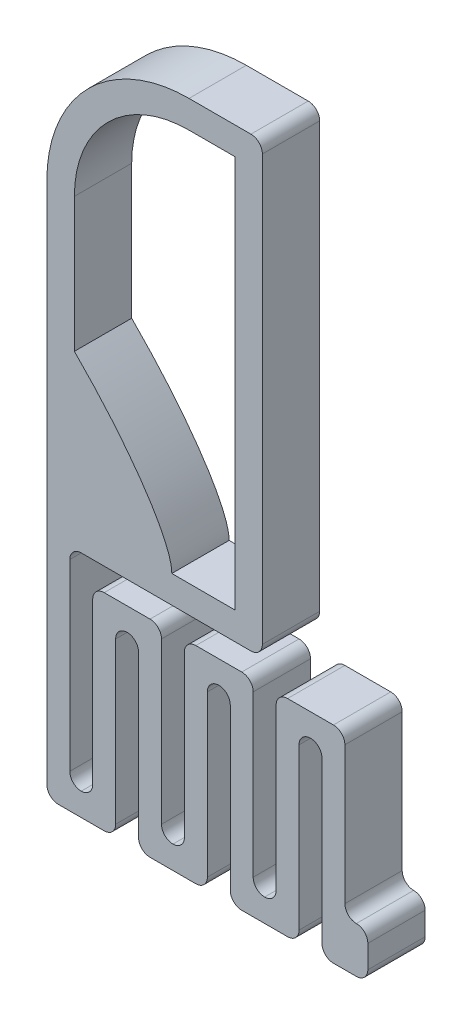
SolidWorks part; units mm, degrees
ref_plane "Front Plane" through (0, 0, 0) normal (0, 0, 1) x (1, 0, 0)
ref_plane "Top Plane" through (0, 0, 0) normal (0, 1, 0) x (1, 0, 0)
ref_plane "Right Plane" through (0, 0, 0) normal (1, 0, 0) x (0, 0, -1)
sketch "Sketch1" plane through (0, 0, 0) normal (0, 0, 1) x (1, 0, 0)
  line L4 (24.1, -2.875) -> (24.1, -9.2268)
  line L5 (28.3497, -16.1955) -> (33.5, -16.2014)
  line L6 (33.5, -16.2014) -> (33.5, 3.325)
  line L7 (33.5, 3.325) -> (30.3, 3.325)
  line L12 (25.1, -2.875) -> (25.1, -8.813)
  line L13 (29.35, -15.1967) -> (32.5, -15.2002)
  line L14 (32.5, -15.2002) -> (32.5, 2.325)
  line L15 (32.5, 2.325) -> (30.3, 2.325)
  arc A1 (30.3, 3.325) -> (24.1, -2.875) centre (30.3, -2.875) ccw
  arc A3 (30.3, 2.325) -> (25.1, -2.875) centre (30.3, -2.875) ccw
  spline S1 degree 1 poles (24.1, -9.2268) (28.3497, -16.1955) knots 0 0 1 1 construction
  spline S3 degree 3 poles (25.1, -8.813) (25.56, -9.2737) (26.0079, -9.7454) (26.867, -10.7224) (27.2796, -11.2269) (28.0593, -12.2678) (28.429, -12.8063) (28.9082, -13.6556) (29.0574, -13.9458) (29.2343, -14.4016) (29.2849, -14.5552) (29.3337, -14.7909) (29.3455, -14.8704) (29.3525, -15.0326) (29.35, -15.1149) (29.35, -15.1967) knots 0 0 0 0 0.25 0.25 0.5 0.5 0.75 0.75 0.875 0.875 0.9375 0.9375 0.96875 0.96875 1 1 1 1
  spline S4 degree 3 poles (24.1, -9.2268) (24.3664, -9.4936) (24.9038, -10.0315) (25.9016, -11.1143) (26.84, -12.2699) (27.5533, -13.3087) (27.913, -13.9181) (28.1082, -14.2907) (28.2331, -14.5811) (28.3067, -14.7774) (28.3485, -14.9651) (28.3517, -14.9723) (28.3497, -15.1803) (28.3501, -15.376) (28.3497, -15.7122) (28.3498, -16.0025) (28.3497, -16.1955) knots -0.052968 -0.052968 -0.052968 -0.052968 0.094559 0.242086 0.53714 0.684667 0.758431 0.832194 0.869076 0.905958 0.94284 0.979721 0.998162 1.016603 1.053485 1.127248 1.127248 1.127248 1.127248
  dimension "D2" = 1
extrude "Boss-Extrude1" add sketch "Sketch1" against normal blind 2.5
ref_plane "Plane1" through (29.35, -15.1967, 0) normal (1, -0.0011, 0) x (0, 0, -1)
sketch "Sketch3" plane through (0, 0, 0) normal (0, 0, 1) x (1, 0, 0)
  line L0 (33.5, -16.2014) -> (37.5, -25.8209)
  line L1 (37.5, -25.8209) -> (36.5766, -26.2048)
  line L2 (36.5766, -26.2048) -> (32.4165, -16.2001)
  line L3 (28.3497, -16.1955) -> (33.5, -16.2014) construction
  line L4 (32.4165, -16.2001) -> (33.5, -16.2014)
  line L5 (33.5, -16.2014) -> (33.5, 3.325) construction
  dimension "D1" = 1
  dimension "D2" = 4
  dimension "D3" = 10
extrude "Boss-Extrude2" [suppressed] add sketch "Sketch3" against normal up to surface (2.5 mm away)
fillet "Fillet1" [suppressed] radius 6
fillet "Fillet2" [suppressed] radius 2
sketch "Sketch4" plane through (0, 0, 0) normal (0, 0, 1) x (1, 0, 0)
  line L37 (32.3, 2.125) -> (30.3, 2.125)
  line L38 (32.3, -15) -> (32.3, 2.125)
  line L39 (29.5504, -14.9969) -> (32.3, -15)
  line L40 (25.3, -2.875) -> (25.3, -8.7304)
  line L41 (32.3, 2.125) -> (30.3, 2.125)
  line L42 (32.3, -15) -> (32.3, 2.125)
  line L43 (29.5504, -14.9969) -> (32.3, -15)
  line L44 (25.3, -2.875) -> (25.3, -8.7304)
  line L49 (33.5, -16.2014) -> (33.5, 3.325)
  line L50 (33.5, 3.325) -> (30.3, 3.325)
  line L51 (24.1, -2.875) -> (24.1, -9.2268)
  line L52 (28.3497, -16.1955) -> (33.5, -16.2014)
  line L55 (33.5, -16.2014) -> (33.5, 3.325)
  line L56 (33.5, 3.325) -> (30.3, 3.325)
  line L57 (24.1, -2.875) -> (24.1, -9.2268)
  line L58 (28.3497, -16.1955) -> (33.5, -16.2014)
  arc A11 (30.3, 2.125) -> (25.3, -2.875) centre (30.3, -2.875) ccw
  arc A12 (30.3, 2.125) -> (25.3, -2.875) centre (30.3, -2.875) ccw
  arc A16 (30.3, 3.325) -> (24.1, -2.875) centre (30.3, -2.875) ccw
  arc A19 (30.3, 3.325) -> (24.1, -2.875) centre (30.3, -2.875) ccw
  spline S9 degree 3 poles (1401.8784, 1440.092) (-108.5339, -18.53) (-1.656, 22.1061) (27.0343, -10.6112) (27.4392, -11.1069) (28.2066, -12.1303) (28.5703, -12.6583) (29.0466, -13.4902) (29.1963, -13.7749) (29.3797, -14.2171) (29.4349, -14.3668) (31.7287, -22.7707) (-5.1078, -46.4987) (-1903.3477, 497.023) knots -16.502204 -16.502204 -16.502204 -16.502204 0.25 0.25 0.5 0.5 0.75 0.75 0.875 0.875 0.9375 0.9375 4.27637 4.27637 4.27637 4.27637 only from (25.3, -8.7304) to (29.5504, -14.9969)
  spline S10 degree 3 poles (25.3, -8.7304) (25.7512, -9.1842) (26.1906, -9.6491) (27.0343, -10.6112) (27.4392, -11.1069) (28.2066, -12.1303) (28.5703, -12.6583) (29.0466, -13.4902) (29.1963, -13.7749) (29.3797, -14.2171) (29.4349, -14.3668) (29.5192, -14.6756) (29.5476, -14.8354) (29.5504, -14.9969) knots 0 0 0 0 0.25 0.25 0.5 0.5 0.75 0.75 0.875 0.875 0.9375 0.9375 1 1 1 1
  spline S11 degree 3 poles (2014.842, -200.1856) (-34.9401, 17.6708) (11.0749, 4.9746) (25.9016, -11.1143) (26.84, -12.2699) (27.5533, -13.3087) (27.913, -13.9181) (28.1082, -14.2907) (28.2331, -14.5811) (28.3067, -14.7774) (28.3485, -14.9651) (28.3517, -14.9723) (28.3497, -15.1803) (28.3501, -15.376) (28.3273, -37.1757) (30.3103, -71.2994) (-301.9361, 1956.2317) knots -8.231302 -8.231302 -8.231302 -8.231302 0.094559 0.242086 0.53714 0.684667 0.758431 0.832194 0.869076 0.905958 0.94284 0.979721 0.998162 1.016603 1.053485 9.369392 9.369392 9.369392 9.369392 only from (24.1, -9.2268) to (28.3497, -16.1955)
  spline S12 degree 3 poles (24.1, -9.2268) (24.3664, -9.4936) (24.9038, -10.0315) (25.9016, -11.1143) (26.84, -12.2699) (27.5533, -13.3087) (27.913, -13.9181) (28.1082, -14.2907) (28.2331, -14.5811) (28.3067, -14.7774) (28.3485, -14.9651) (28.3517, -14.9723) (28.3497, -15.1803) (28.3501, -15.376) (28.3497, -15.7122) (28.3498, -16.0025) (28.3497, -16.1955) knots -0.052968 -0.052968 -0.052968 -0.052968 0.094559 0.242086 0.53714 0.684667 0.758431 0.832194 0.869076 0.905958 0.94284 0.979721 0.998162 1.016603 1.053485 1.127248 1.127248 1.127248 1.127248
  dimension "D1" = 0.2
  dimension "D2" = 0
extrude "Boss-Extrude3" add sketch "Sketch4" against normal up to surface (2.5 mm away) up to face at (28.3455, -5.0326, -2.5)
sketch "Sketch5" plane through (0, 0, 0) normal (0, 0, 1) x (1, 0, 0)
  line L0 (24.1, -9.2268) -> (24.1, -16.1955)
  line L1 (24.1, -16.1955) -> (28.3497, -16.1955)
  line L2 (24.1, -16.1955) -> (24.1, -26.1955)
  line L3 (25.1, -16.1955) -> (25.1, -25.1955)
  line L4 (25.1, -26.1955) -> (24.1, -26.1955)
  line L5 (25.1, -26.1955) -> (27.1, -26.1955)
  line L6 (27.1, -26.1955) -> (27.1, -18.1955)
  line L7 (27.1, -17.1955) -> (26.1, -17.1955)
  line L8 (26.1, -17.1955) -> (26.1, -25.1955)
  line L9 (26.1, -25.1955) -> (25.1, -25.1955)
  line L10 (27.1, -17.1955) -> (29.1, -17.1955)
  line L11 (29.1, -17.1955) -> (29.1, -25.1955)
  line L12 (29.1, -26.1955) -> (28.1, -26.1955)
  line L13 (28.1, -26.1955) -> (28.1, -18.1955)
  line L14 (28.1, -18.1955) -> (27.1, -18.1955)
  line L15 (29.1, -26.1955) -> (31.1, -26.1955)
  line L16 (31.1, -26.1955) -> (31.1, -18.1955)
  line L17 (31.1, -17.1955) -> (30.1, -17.1955)
  line L18 (30.1, -17.1955) -> (30.1, -25.1955)
  line L19 (30.1, -25.1955) -> (29.1, -25.1955)
  line L20 (31.1, -17.1955) -> (33.1, -17.1955)
  line L21 (33.1, -17.1955) -> (33.1, -25.1955)
  line L22 (33.1, -26.1955) -> (32.1, -26.1955)
  line L23 (32.1, -26.1955) -> (32.1, -18.1955)
  line L24 (32.1, -18.1955) -> (31.1, -18.1955)
  line L25 (33.1, -26.1955) -> (35.1, -26.1955)
  line L26 (35.1, -26.1955) -> (35.1, -18.1955)
  line L27 (35.1, -17.1955) -> (34.1, -17.1955)
  line L28 (34.1, -17.1955) -> (34.1, -25.1955)
  line L29 (34.1, -25.1955) -> (33.1, -25.1955)
  line L30 (35.1, -17.1955) -> (37.1, -17.1955)
  line L31 (37.1, -17.1955) -> (37.1, -24.1955)
  line L32 (37.1, -26.1955) -> (36.1, -26.1955)
  line L33 (36.1, -26.1955) -> (36.1, -18.1955)
  line L34 (36.1, -18.1955) -> (35.1, -18.1955)
  line L35 (37.1, -26.1955) -> (38.1, -26.1955)
  line L36 (38.1, -26.1955) -> (38.1, -24.1955)
  line L37 (38.1, -24.1955) -> (37.1, -24.1955)
  spline S0 degree 3 poles (2014.842, -200.1856) (-34.9401, 17.6708) (11.0749, 4.9746) (25.9016, -11.1143) (26.84, -12.2699) (27.5533, -13.3087) (27.913, -13.9181) (28.1082, -14.2907) (28.2331, -14.5811) (28.3067, -14.7774) (28.3485, -14.9651) (28.3517, -14.9723) (28.3497, -15.1803) (28.3501, -15.376) (28.3273, -37.1757) (30.3103, -71.2994) (-301.9361, 1956.2317) knots -8.231302 -8.231302 -8.231302 -8.231302 0.094559 0.242086 0.53714 0.684667 0.758431 0.832194 0.869076 0.905958 0.94284 0.979721 0.998162 1.016603 1.053485 9.369392 9.369392 9.369392 9.369392 only from (24.1, -9.2268) to (28.3497, -16.1955) construction
  spline S1 degree 3 poles (24.1, -9.2268) (24.3664, -9.4936) (24.9038, -10.0315) (25.9016, -11.1143) (26.84, -12.2699) (27.5533, -13.3087) (27.913, -13.9181) (28.1082, -14.2907) (28.2331, -14.5811) (28.3067, -14.7774) (28.3485, -14.9651) (28.3517, -14.9723) (28.3497, -15.1803) (28.3501, -15.376) (28.3497, -15.7122) (28.3498, -16.0025) (28.3497, -16.1955) knots -0.052968 -0.052968 -0.052968 -0.052968 0.094559 0.242086 0.53714 0.684667 0.758431 0.832194 0.869076 0.905958 0.94284 0.979721 0.998162 1.016603 1.053485 1.127248 1.127248 1.127248 1.127248
  spline M16 degree 3 poles (24.1, -9.2268) (24.3664, -9.4936) (24.9038, -10.0315) (25.9016, -11.1143) (26.84, -12.2699) (27.5533, -13.3087) (27.913, -13.9181) (28.1082, -14.2907) (28.2331, -14.5811) (28.3067, -14.7774) (28.3485, -14.9651) (28.3517, -14.9723) (28.3497, -15.1803) (28.3501, -15.376) (28.3497, -15.7122) (28.3498, -16.0025) (28.3497, -16.1955) knots -0.052968 -0.052968 -0.052968 -0.052968 0.094559 0.242086 0.53714 0.684667 0.758431 0.832194 0.869076 0.905958 0.94284 0.979721 0.998162 1.016603 1.053485 1.127248 1.127248 1.127248 1.127248
  dimension "D1" = 1
  dimension "D2" = 10
  dimension "D3" = 1
  dimension "D4" = 1
  dimension "D5" = 1
extrude "Boss-Extrude4" add sketch "Sketch5" against normal up to surface (2.5 mm away) contours L36 L37 L31 L30 L27 L28 L29 L21 L20 L17 L18 L19 L11 L10 L7 L8 L9 L3 L1 L2 L4 L5 L6 L14 L13 L12 L15 L16 L24 L23 L22 L25 L26 L34 L33 L32 L35 | L0 L1 M16 region at (25.8033, -13.6639, 0) region at (30.7111, -21.7233, 0) up to face at (28.4068, -5.5134, -2.5)
fillet "Fillet3" radius 0.5 31 edges at (24.1, -26.1955, -1.25) (27.1, -26.1955, -1.25) (27.1, -18.1955, -1.25) (28.1, -18.1955, -1.25) (28.1, -26.1955, -1.25) (31.1, -26.1955, -1.25) (31.1, -18.1955, -1.25) (32.1, -18.1955, -1.25) (32.1, -26.1955, -1.25) (35.1, -26.1955, -1.25) (35.1, -18.1955, -1.25) (36.1, -18.1955, -1.25) (36.1, -26.1955, -1.25) (38.1, -26.1955, -1.25) (38.1, -24.1955, -1.25) (37.1, -24.1955, -1.25) (37.1, -17.1955, -1.25) (34.1, -17.1955, -1.25) (34.1, -25.1955, -1.25) (33.1, -25.1955, -1.25) (33.1, -17.1955, -1.25) (30.1, -17.1955, -1.25) (30.1, -25.1955, -1.25) (29.1, -25.1955, -1.25) (26.1, -17.1955, -1.25) (26.1, -25.1955, -1.25) (25.1, -25.1955, -1.25) (25.1, -16.1955, -1.25) (33.5, -16.2014, -1.25) (33.5, 3.325, -1.25) (29.1, -17.1955, -1.25)
